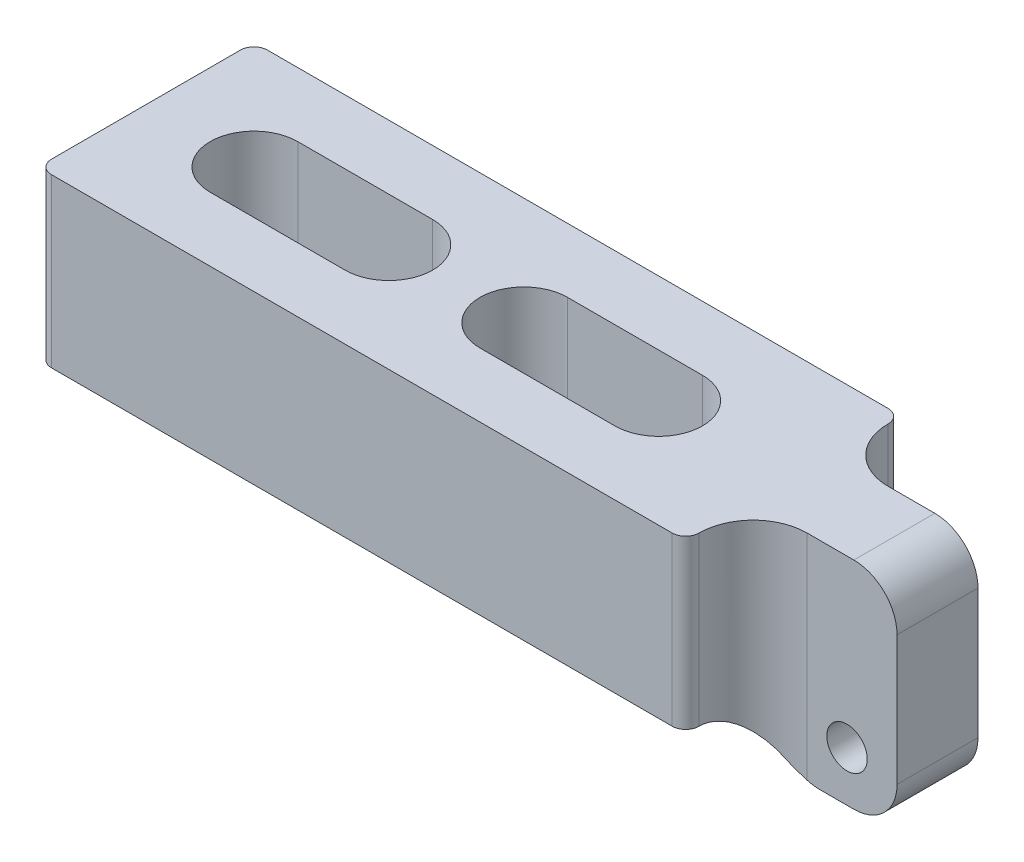
SolidWorks part; units mm, degrees
material "6061 Alloy"
ref_plane "Front" through (0, 0, 0) normal (0, 0, 1) x (1, 0, 0)
ref_plane "Top" through (0, 0, 0) normal (0, 1, 0) x (1, 0, 0)
ref_plane "Right" through (0, 0, 0) normal (1, 0, 0) x (0, 0, -1)
sketch "Sketch1" plane through (0, 0, 0) normal (0, 0, 1) x (1, 0, 0)
  line L0 (0, 0) -> (6.35, 0) construction
  line L1 (2.9436, -2.9436) -> (2.9436, 9.7564)
  line L2 (2.9436, 9.7564) -> (-43.6238, 9.7564)
  line L3 (-43.6238, 9.7564) -> (-43.6238, -0.0889)
  line L4 (-43.6238, -0.0889) -> (-5.5238, -0.0889)
  line L5 (-5.5238, -0.0889) -> (-2.6691, -2.9436)
  line L6 (-2.6691, -2.9436) -> (2.9436, -2.9436)
  line L7 (-43.6238, -6.4389) -> (2.9436, -6.4389) construction
  circle A0 centre (0, 0) radius 1.1906
  circle A1 centre (0, 0) radius 2.9436 construction
  circle A2 centre (6.35, 0) radius 2.9436 construction
  dimension "D1" = 2.3813
  dimension "D2" = 6.35
  dimension "D3" = 5.8872
  dimension "D4" = 12.7
  dimension "D5" = 3.9688
  dimension "D6" = 38.1
  dimension "D7" = 45
  dimension "D8" = 6.35
  dimension "D9" = 6.4389
extrude "Boss-Extrude1" add sketch "Sketch1" along normal blind 12.7
sketch "Sketch5" plane through (0, -2.9436, 0) normal (0, -1, 0) x (1, 0, 0)
  line L0 (-5.5238, 6.35) -> (2.9436, 6.35) construction
  line L1 (-5.5238, 12.7) -> (-5.5238, 0) construction
  line L2 (2.9436, 12.7) -> (2.9436, 0) construction
  line L4 (2.9436, 12.7) -> (-5.5238, 12.7)
  line L5 (2.9436, 12.7) -> (2.9436, 8.7312)
  line L6 (2.9436, 8.7312) -> (-5.5238, 8.7313)
  line L7 (-5.5238, 12.7) -> (-5.5238, 8.7313)
  line L9 (2.9436, 0) -> (-5.5238, 0)
  line L10 (2.9436, 0) -> (2.9436, 3.9688)
  line L11 (2.9436, 3.9688) -> (-5.5238, 3.9687)
  line L12 (-5.5238, 0) -> (-5.5238, 3.9687)
  dimension "D2" = 4.7625
extrude "Cut-Extrude2" cut sketch "Sketch5" against normal through all
fillet "Fillet1" radius 2.54 3 edges at (-2.6691, -2.9436, 6.35) (2.9436, -2.9436, 6.35) (2.9436, 9.7564, 6.35)
hole_wizard "#10 Clearance Hole1" [suppressed] positions "Sketch8" profile "Sketch7" hole size "#10" standard "ANSI Inch"
sketch "Sketch8" plane through (0, -0.0889, 0) normal (0, -1, 0) x (-1, 0, 0)
  line L0 (5.5238, -6.35) -> (37.2738, -6.35) construction
  line L1 (5.5238, -8.7313) -> (5.5238, -3.9687) construction
  line L2 (37.2738, -12.7) -> (37.2738, 0) construction
  line L4 (16.2109, -11.1125) -> (18.9605, -6.35) construction
  line L5 (18.9605, -6.35) -> (16.2109, -1.5875) construction
  line L6 (16.2109, -1.5875) -> (10.7116, -1.5875) construction
  line L7 (10.7116, -1.5875) -> (7.962, -6.35) construction
  line L8 (7.962, -6.35) -> (10.7116, -11.1125) construction
  line L9 (10.7116, -11.1125) -> (16.2109, -11.1125) construction
  line L11 (32.0859, -11.1125) -> (34.8355, -6.35) construction
  line L12 (34.8355, -6.35) -> (32.0859, -1.5875) construction
  line L13 (32.0859, -1.5875) -> (26.5866, -1.5875) construction
  line L14 (26.5866, -1.5875) -> (23.837, -6.35) construction
  line L15 (23.837, -6.35) -> (26.5866, -11.1125) construction
  line L16 (26.5866, -11.1125) -> (32.0859, -11.1125) construction
  circle A0 centre (13.4613, -6.35) radius 4.7625 construction
  circle A1 centre (29.3363, -6.35) radius 4.7625 construction
  point P10 (13.4613, -6.35)
  point P12 (29.3363, -6.35)
  point P15 (21.3988, -6.35)
  dimension "D3" = 9.525
  dimension "D1" = 7.9375
  dimension "D2" = 7.9375
sketch "Sketch7" plane through (-29.3363, -0.0889, 6.35) normal (1, 0, 0) x (0, 0, -1)
  line L0 (0, 0) -> (0, 9.8453)
  line L1 (0, 9.8453) -> (2.5527, 9.8453)
  line L2 (2.5527, 9.8453) -> (2.5527, 0)
  line L5 (2.5527, 0) -> (0, 0)
  line L11 (0, -6.35) -> (0, 107.95) construction
  dimension "Thru Hole Dia." = 5.1054
  dimension "Thru Hole Depth" = 9.8453
fillet "Fillet2" radius 3.175 2 edges at (-5.5238, 4.8338, 8.7313) (-5.5238, 4.8338, 3.9687)
sketch "Sketch9" plane through (0, 9.7564, 0) normal (0, 1, 0) x (1, 0, 0)
  line L0 (-43.6238, -6.35) -> (0.4036, -6.35) construction
  line L1 (-43.6238, -12.7) -> (-43.6238, 0) construction
  line L2 (0.4036, -8.7312) -> (0.4036, -3.9687) construction
  line L3 (-37.2738, -6.35) -> (-29.3363, -6.35) construction
  line L4 (-37.2738, -3.7719) -> (-29.3363, -3.7719)
  line L5 (-37.2738, -8.9281) -> (-29.3363, -8.9281)
  line L6 (-21.3988, -6.35) -> (-13.4613, -6.35) construction
  line L7 (-21.3988, -3.7719) -> (-13.4613, -3.7719)
  line L8 (-21.3988, -8.9281) -> (-13.4613, -8.9281)
  line L9 (-5.5238, -12.7) -> (-5.5238, -11.9063) construction
  arc A0 (-37.2738, -3.7719) -> (-37.2738, -8.9281) centre (-37.2738, -6.35) ccw
  arc A1 (-29.3363, -8.9281) -> (-29.3363, -3.7719) centre (-29.3363, -6.35) ccw
  arc A2 (-21.3988, -3.7719) -> (-21.3988, -8.9281) centre (-21.3988, -6.35) ccw
  arc A3 (-13.4613, -8.9281) -> (-13.4613, -3.7719) centre (-13.4613, -6.35) ccw
  point P8 (-33.305, -6.35)
  point P14 (-17.43, -6.35)
  point P23 (-5.5238, -12.3031)
  dimension "D1" = 15.875
  dimension "D2" = 7.9375
  dimension "D3" = 5.1562
  dimension "D4" = 7.9375
extrude "Cut-Extrude3" cut sketch "Sketch9" against normal through all
fillet "Fillet3" radius 0.7937 4 edges at (-43.6238, 4.8338, 12.7) (-43.6238, 4.8338, 0) (-5.5238, 4.8338, 12.7) (-5.5238, 4.8338, 0)
